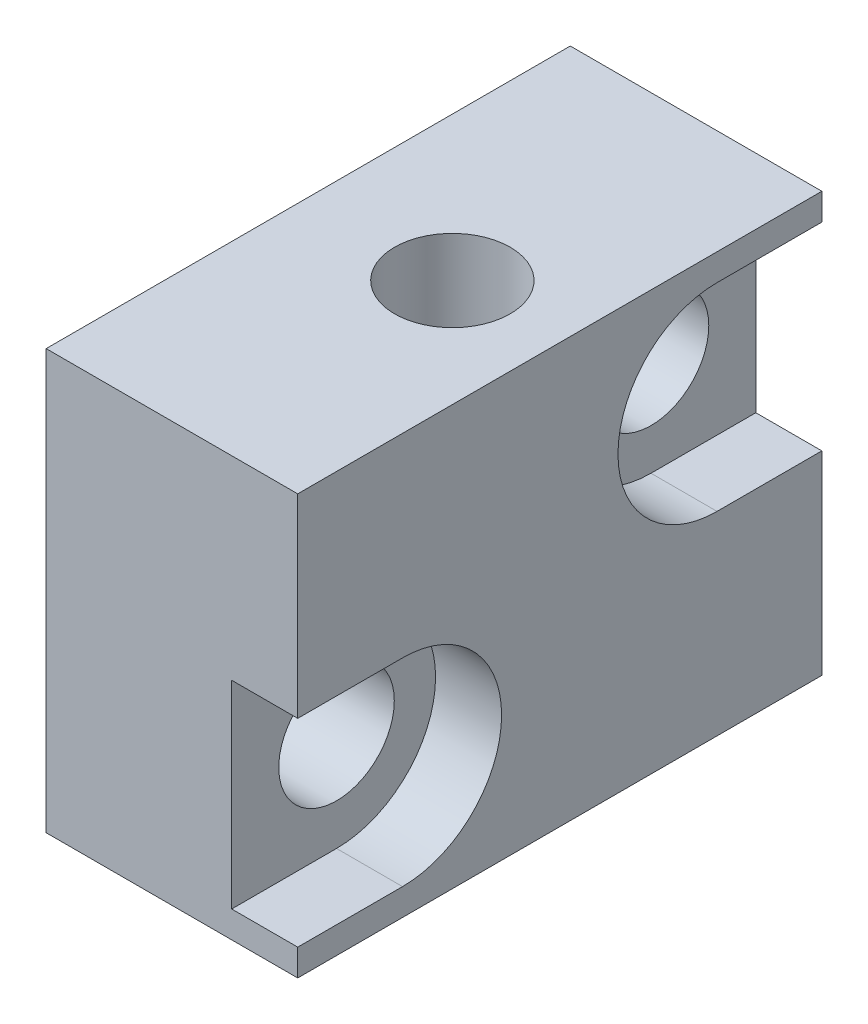
SolidWorks part; units mm, degrees
material "PET"
ref_plane "Front Plane" through (0, 0, 0) normal (1, 0, 0) x (0, 1, 0)
ref_plane "Top Plane" through (0, 0, 0) normal (0, 0, 1) x (0, 1, 0)
ref_plane "Right Plane" through (0, 0, 0) normal (0, 1, 0) x (-1, 0, 0)
sketch "Sketch1" plane through (0, 0, 0) normal (1, 0, 0) x (0, 1, 0)
  line L1 (6.35, -7.9375) -> (-6.35, -7.9375)
  line L2 (6.35, -7.9375) -> (6.35, 7.9375)
  line L3 (6.35, 7.9375) -> (-6.35, 7.9375)
  line L4 (-6.35, -7.9375) -> (-6.35, 7.9375)
  line L5 (6.35, -7.9375) -> (-6.35, 7.9375) construction
  line L6 (6.35, 7.9375) -> (-6.35, -7.9375) construction
  point P0 (0, 0)
  dimension "D1" = 15.875
  dimension "D2" = 12.7
extrude "Boss-Extrude1" add sketch "Sketch1" along normal blind 7.62
sketch "Sketch3" plane through (0, -6.35, 0) normal (0, -1, 0) x (1, 0, 0)
  line L10 (0, 7.9375) -> (0, -7.9375)
  line L11 (0, -7.9375) -> (7.62, -7.9375)
  line L12 (7.62, -7.9375) -> (7.62, 7.9375)
  line L13 (7.62, 7.9375) -> (0, 7.9375)
  line L14 (0, 7.9375) -> (0, -7.9375)
  line L15 (0, -7.9375) -> (7.62, -7.9375)
  line L16 (7.62, -7.9375) -> (7.62, 7.9375)
  line L17 (7.62, 7.9375) -> (0, 7.9375)
  circle A0 centre (4.3663, 0) radius 1.75
  circle A1 centre (4.3663, 0) radius 5 construction
  circle A2 centre (4.3663, 0) radius 3 construction
  point P2 (9.3663, 0)
  point P3 (2.6163, 0)
  point P6 (-6.35, 0)
  dimension "D1" = 3.5
  dimension "D2" = 10
  dimension "D6" = 6
  dimension "D3" = 15.7163
  dimension "D4" = 6.35
  dimension "D5" = 0
extrude "Cut-Extrude1" cut sketch "Sketch3" against normal blind 22.2885 contours A0 region at (4.3663, -6.35, 0)
sketch "Sketch4" plane through (7.62, 0, 0) normal (1, 0, 0) x (0, 1, 0)
  line L0 (-6.35, 7.9375) -> (-6.35, -7.9375) construction
  line L1 (2.54, -4.7625) -> (-2.54, -4.7625) construction
  line L2 (2.54, -4.7625) -> (2.54, 4.7625) construction
  line L3 (2.54, 4.7625) -> (-2.54, 4.7625) construction
  line L4 (-2.54, -4.7625) -> (-2.54, 4.7625) construction
  line L5 (2.54, -4.7625) -> (-2.54, 4.7625) construction
  line L6 (2.54, 4.7625) -> (-2.54, -4.7625) construction
  line L7 (6.35, 7.9375) -> (-6.35, 7.9375) construction
  circle A5 centre (-2.54, 4.7625) radius 1.75
  circle A6 centre (2.54, -4.7625) radius 1.75
  point P0 (0, 0)
  dimension "D3" = 3.5
  dimension "D1" = 3.81
  dimension "D2" = 3.175
extrude "Cut-Extrude2" cut sketch "Sketch4" against normal blind 22.2885 contours A5 | A6 region at (7.62, -2.54, 4.7625) region at (7.62, 2.54, -4.7625)
sketch "Sketch5" plane through (7.62, 0, 0) normal (1, 0, 0) x (0, 1, 0)
  line L0 (-5.54, 4.7625) -> (-5.54, 7.9375)
  line L1 (6.35, 7.9375) -> (-6.35, 7.9375) construction
  line L2 (-5.54, 7.9375) -> (0.46, 7.9375)
  line L3 (0.46, 7.9375) -> (0.46, 4.7625)
  line L4 (5.54, -4.7625) -> (5.54, -7.9375)
  line L5 (-6.35, -7.9375) -> (6.35, -7.9375) construction
  line L6 (5.54, -7.9375) -> (-0.46, -7.9375)
  line L7 (-0.46, -7.9375) -> (-0.46, -4.7625)
  line L8 (-2.54, 1.7625) -> (-6.35, 1.7625)
  line L9 (-6.35, 7.9375) -> (-6.35, -7.9375) construction
  circle A0 centre (2.54, -4.7625) radius 1.75 construction
  circle A1 centre (-2.54, 4.7625) radius 1.75 construction
  circle A2 centre (2.54, -4.7625) radius 1.75 construction
  circle A3 centre (-2.54, 4.7625) radius 1.75 construction
  circle A4 centre (-2.54, 4.7625) radius 3
  circle A5 centre (2.54, -4.7625) radius 3
  circle M3 centre (-2.54, 4.7625) radius 1.75
  circle M4 centre (2.54, -4.7625) radius 1.75
  line M6 (-6.35, -7.9375) -> (6.35, -7.9375)
  line M8 (6.35, 7.9375) -> (-6.35, 7.9375)
  dimension "D1" = 6
extrude "Cut-Extrude3" cut sketch "Sketch5" against normal blind 2 contours A4 M3 | A4 L3 L0 M8 | A5 M4 | A5 L7 L4 M6 region at (7.62, -5.4721, 6.35) region at (7.62, -2.54, 7.6776) region at (7.62, 2.54, -7.6776) region at (7.62, 5.4721, -6.35)
